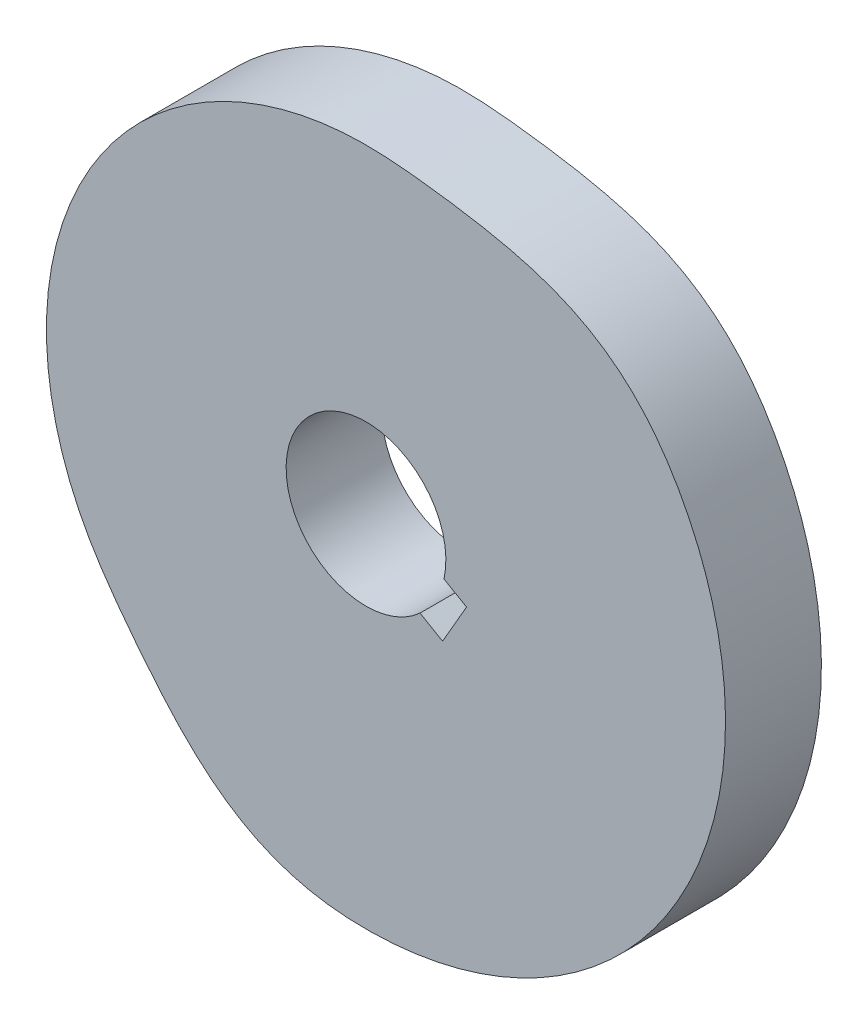
SolidWorks part; units mm, degrees
material "45"
ref_plane "前视基准面" through (0, 0, 0) normal (0, 0, 1) x (1, 0, 0)
ref_plane "上视基准面" through (0, 0, 0) normal (0, 1, 0) x (1, 0, 0)
ref_plane "右视基准面" through (0, 0, 0) normal (1, 0, 0) x (0, 0, -1)
ref_axis "基准轴1" through (0, 0, -88.99) along (0, 0, 1)
sketch "草图1" plane through (0, 0, 0) normal (0, 0, 1) x (1, 0, 0)
  arc A0 (38.9711, 22.5) -> (0, -45) centre (0, 0) cw construction
  arc A1 (-34.641, -20) -> (0, 40) centre (0, 0) cw construction
  spline S0 degree 3 poles (0, 40) (0.4654, 40) (1.1636, 39.9878) (2.0938, 39.9508) (2.7911, 39.9136) (3.488, 39.8678) (4.1847, 39.8141) (4.8813, 39.7534) (5.5777, 39.6862) (6.2744, 39.6133) (6.9714, 39.535) (7.6691, 39.452) (8.3677, 39.3644) (9.0674, 39.2725) (9.7685, 39.1765) (10.4712, 39.0763) (11.1759, 38.9719) (11.8826, 38.8631) (12.5915, 38.7497) (13.3028, 38.6311) (14.0164, 38.507) (14.7325, 38.3767) (15.4509, 38.2398) (16.1715, 38.0953) (16.8942, 37.9427) (17.6185, 37.7811) (18.3443, 37.6096) (19.071, 37.4274) (19.7982, 37.2337) (20.5253, 37.0275) (21.2516, 36.808) (21.9765, 36.5744) (22.6992, 36.3259) (23.4189, 36.0617) (24.1348, 35.7812) (24.846, 35.4838) (25.5515, 35.1688) (26.2505, 34.8359) (26.9421, 34.4846) (27.6253, 34.1148) (28.2992, 33.7261) (28.963, 33.3186) (29.6159, 32.8922) (30.257, 32.447) (30.8856, 31.9833) (31.5011, 31.5014) (32.1029, 31.0017) (32.6905, 30.4846) (33.2634, 29.9507) (33.8214, 29.4007) (34.3642, 28.8351) (34.8917, 28.2548) (35.4038, 27.6605) (35.9006, 27.053) (36.3822, 26.4332) (36.8489, 25.8019) (37.3011, 25.1599) (37.739, 24.508) (38.3048, 23.6268) (38.7094, 22.9534) (38.9711, 22.5) knots 0 0 0 0 0.031081 0.046623 0.062166 0.077714 0.093267 0.108829 0.124403 0.139994 0.155606 0.171244 0.186914 0.202621 0.218372 0.234172 0.250026 0.265941 0.281921 0.297971 0.314095 0.330296 0.346575 0.362935 0.379376 0.395897 0.412497 0.429175 0.445928 0.462751 0.479642 0.496597 0.513609 0.530676 0.547791 0.564951 0.58215 0.599385 0.616651 0.633944 0.65126 0.668598 0.685954 0.703326 0.720713 0.738112 0.755523 0.772944 0.790375 0.807815 0.825262 0.842717 0.860179 0.877645 0.895117 0.912593 0.930071 0.947552 0.965034 1 1 1 1 construction
  spline S1 degree 3 poles (0, -45) (-0.5236, -45) (-1.309, -44.9863) (-2.355, -44.937) (-3.1386, -44.8836) (-3.9206, -44.8131) (-4.7007, -44.7245) (-5.4783, -44.6173) (-6.2528, -44.4908) (-7.0235, -44.3445) (-7.7898, -44.1778) (-8.551, -43.9905) (-9.3064, -43.7823) (-10.0552, -43.5531) (-10.7968, -43.3028) (-11.5305, -43.0315) (-12.2556, -42.7394) (-12.9715, -42.4268) (-13.6775, -42.0942) (-14.3732, -41.742) (-15.058, -41.3709) (-15.7316, -40.9816) (-16.3935, -40.5748) (-17.0435, -40.1516) (-17.6813, -39.7127) (-18.3069, -39.2591) (-18.9201, -38.792) (-19.5209, -38.3122) (-20.1096, -37.821) (-20.6861, -37.3194) (-21.2509, -36.8084) (-21.8041, -36.2891) (-22.3462, -35.7626) (-22.8776, -35.2297) (-23.3987, -34.6914) (-23.9101, -34.1486) (-24.4123, -33.6021) (-24.9058, -33.0526) (-25.3912, -32.5008) (-25.869, -31.9471) (-26.3398, -31.3921) (-26.8041, -30.8361) (-27.2624, -30.2794) (-27.7152, -29.7222) (-28.1627, -29.1645) (-28.6055, -28.6065) (-29.0436, -28.048) (-29.4773, -27.4888) (-29.9067, -26.9288) (-30.3318, -26.3676) (-30.7526, -25.805) (-31.1689, -25.2404) (-31.5804, -24.6736) (-31.9868, -24.104) (-32.3877, -23.5311) (-32.7825, -22.9546) (-33.1707, -22.374) (-33.5516, -21.7887) (-34.0487, -21.0016) (-34.4083, -20.4031) (-34.641, -20) knots 0 0 0 0 0.034966 0.052448 0.069929 0.087407 0.104883 0.122355 0.139821 0.157283 0.174738 0.192185 0.209625 0.227056 0.244477 0.261888 0.279287 0.296674 0.314046 0.331402 0.34874 0.366056 0.383349 0.400615 0.41785 0.435049 0.452209 0.469324 0.486391 0.503403 0.520358 0.537249 0.554072 0.570825 0.587503 0.604103 0.620624 0.637065 0.653425 0.669704 0.685905 0.702029 0.718079 0.734059 0.749974 0.765828 0.781628 0.797379 0.813086 0.828756 0.844394 0.860006 0.875597 0.891171 0.906733 0.922286 0.937834 0.953377 0.968919 1 1 1 1 construction
  spline S2 degree 3 poles (41.6041, 17.1493) (53.8438, -12.544) (37.7853, -40.3581) (5.9503, -44.6049) (4.6444, -44.7791) (2.0174, -45.0128) (-1.9795, -45.0232) (-4.6067, -44.7608) (-5.9066, -44.5465) (-6.0219, -44.5275) (-6.3949, -44.4638) (-7.0235, -44.3445) (-7.7898, -44.1778) (-8.551, -43.9905) (-9.3064, -43.7823) (-10.0552, -43.5531) (-10.7968, -43.3028) (-11.5305, -43.0315) (-12.2556, -42.7394) (-12.9715, -42.4268) (-13.6775, -42.0942) (-14.3732, -41.742) (-15.058, -41.3709) (-15.7316, -40.9816) (-16.3935, -40.5748) (-17.0435, -40.1516) (-17.6813, -39.7127) (-18.3069, -39.2591) (-18.9201, -38.792) (-19.5209, -38.3122) (-20.1096, -37.821) (-20.6861, -37.3194) (-21.2509, -36.8084) (-21.8041, -36.2891) (-22.3462, -35.7626) (-22.8776, -35.2297) (-23.3987, -34.6914) (-23.9101, -34.1486) (-24.4123, -33.6021) (-24.9058, -33.0526) (-25.3912, -32.5008) (-25.869, -31.9471) (-26.3398, -31.3921) (-26.8041, -30.8361) (-27.2624, -30.2794) (-27.7152, -29.7222) (-28.1627, -29.1645) (-28.6055, -28.6065) (-29.0436, -28.048) (-29.4773, -27.4888) (-29.9067, -26.9288) (-30.3318, -26.3676) (-30.7526, -25.805) (-31.1689, -25.2404) (-31.5804, -24.6736) (-31.9868, -24.104) (-32.3877, -23.5311) (-32.7825, -22.9546) (-33.1707, -22.374) (-33.4631, -21.9247) (-33.6262, -21.6691) (-33.664, -21.6096) (-33.8895, -21.2546) (-34.3315, -20.539) (-34.9631, -19.4452) (-35.3603, -18.7037) (-35.553, -18.3299) (-50.3714, 10.4121) (-34.2028, 38.4168) (-1.9024, 39.9547) (-1.4823, 39.9747) (-0.6415, 40.0015) (0.6215, 40.0015) (1.4623, 39.9765) (1.8825, 39.9587) (1.9529, 39.9557) (2.2558, 39.9422) (2.7911, 39.9136) (3.488, 39.8678) (4.1847, 39.8141) (4.8813, 39.7534) (5.5777, 39.6862) (6.2744, 39.6133) (6.9714, 39.535) (7.6691, 39.452) (8.3677, 39.3644) (9.0674, 39.2725) (9.7685, 39.1765) (10.4712, 39.0763) (11.1759, 38.9719) (11.8826, 38.8631) (12.5915, 38.7497) (13.3028, 38.6311) (14.0164, 38.507) (14.7325, 38.3767) (15.4509, 38.2398) (16.1715, 38.0953) (16.8942, 37.9427) (17.6185, 37.7811) (18.3443, 37.6096) (19.071, 37.4274) (19.7982, 37.2337) (20.5253, 37.0275) (21.2516, 36.808) (21.9765, 36.5744) (22.6992, 36.3259) (23.4189, 36.0617) (24.1348, 35.7812) (24.846, 35.4838) (25.5515, 35.1688) (26.2505, 34.8359) (26.9421, 34.4846) (27.6253, 34.1148) (28.2992, 33.7261) (28.963, 33.3186) (29.6159, 32.8922) (30.257, 32.447) (30.8856, 31.9833) (31.5011, 31.5014) (32.1029, 31.0017) (32.6905, 30.4846) (33.2634, 29.9507) (33.8214, 29.4007) (34.3642, 28.8351) (34.8917, 28.2548) (35.3094, 27.7701) (35.551, 27.4789) (35.6251, 27.3885) (36.4606, 26.3699) (38.0015, 24.2259) (39.9909, 20.7593) (41.102, 18.3674) (41.6041, 17.1493) (53.8438, -12.544) (37.7853, -40.3581) knots -0.01619 0 0 0 0.292107 0.292107 0.292107 0.308297 0.324488 0.340678 0.340678 0.340678 0.342115 0.345328 0.348541 0.351751 0.354961 0.358169 0.361375 0.364579 0.367781 0.37098 0.374177 0.377371 0.380562 0.383749 0.386931 0.390108 0.39328 0.396445 0.399603 0.402753 0.405894 0.409025 0.412145 0.415253 0.418349 0.421432 0.424501 0.427556 0.430597 0.433622 0.436633 0.439629 0.44261 0.445577 0.448531 0.451472 0.454401 0.457318 0.460226 0.463124 0.466015 0.468899 0.471777 0.47465 0.477519 0.480385 0.483249 0.486111 0.488972 0.491833 0.492699 0.492699 0.492699 0.497867 0.503035 0.508203 0.508203 0.508203 0.783903 0.783903 0.783903 0.789072 0.79424 0.799408 0.799408 0.799408 0.800274 0.803134 0.805996 0.808858 0.811722 0.814588 0.817457 0.82033 0.823208 0.826092 0.828982 0.831881 0.834788 0.837706 0.840635 0.843576 0.846529 0.849497 0.852478 0.855474 0.858485 0.86151 0.864551 0.867606 0.870675 0.873758 0.876854 0.879962 0.883082 0.886213 0.889354 0.892504 0.895661 0.898827 0.901998 0.905176 0.908358 0.911545 0.914735 0.917929 0.921126 0.924326 0.927528 0.930732 0.933938 0.937146 0.940355 0.943566 0.946778 0.949992 0.951429 0.951429 0.951429 0.967619 0.98381 1 1 1 1.292107 1.292107 1.292107 weights 1 0.740082 0.740082 1 1 1 1 1 1 1 1 1 1 1 1 1 1 1 1 1 1 1 1 1 1 1 1 1 1 1 1 1 1 1 1 1 1 1 1 1 1 1 1 1 1 1 1 1 1 1 1 1 1 1 1 1 1 1 1 1 1 1 1 1 1 1 1 0.693748 0.693748 1 1 1 1 1 1 1 1 1 1 1 1 1 1 1 1 1 1 1 1 1 1 1 1 1 1 1 1 1 1 1 1 1 1 1 1 1 1 1 1 1 1 1 1 1 1 1 1 1 1 1 1 1 1 1 1 1 1 1 1 1 1 1 1 0.740082 0.740082 only from (41.6041, 17.1493) to (41.6041, 17.1493)
extrude "凸台-拉伸1" add sketch "草图1" along normal blind 12
sketch "草图2" plane through (0, 0, 0) normal (0, 0, 1) x (1, 0, 0)
  line L0 (9.7614, -2.1716) -> (12.5851, -3.8019)
  line L1 (12.5851, -3.8019) -> (9.5851, -8.9981)
  line L2 (9.5851, -8.9981) -> (6.7614, -7.3678)
  arc A0 (9.7614, -2.1716) -> (6.7614, -7.3678) centre (0, 0) ccw
extrude "切除-拉伸1" cut sketch "草图2" against normal blind 12 and the other way blind 12
